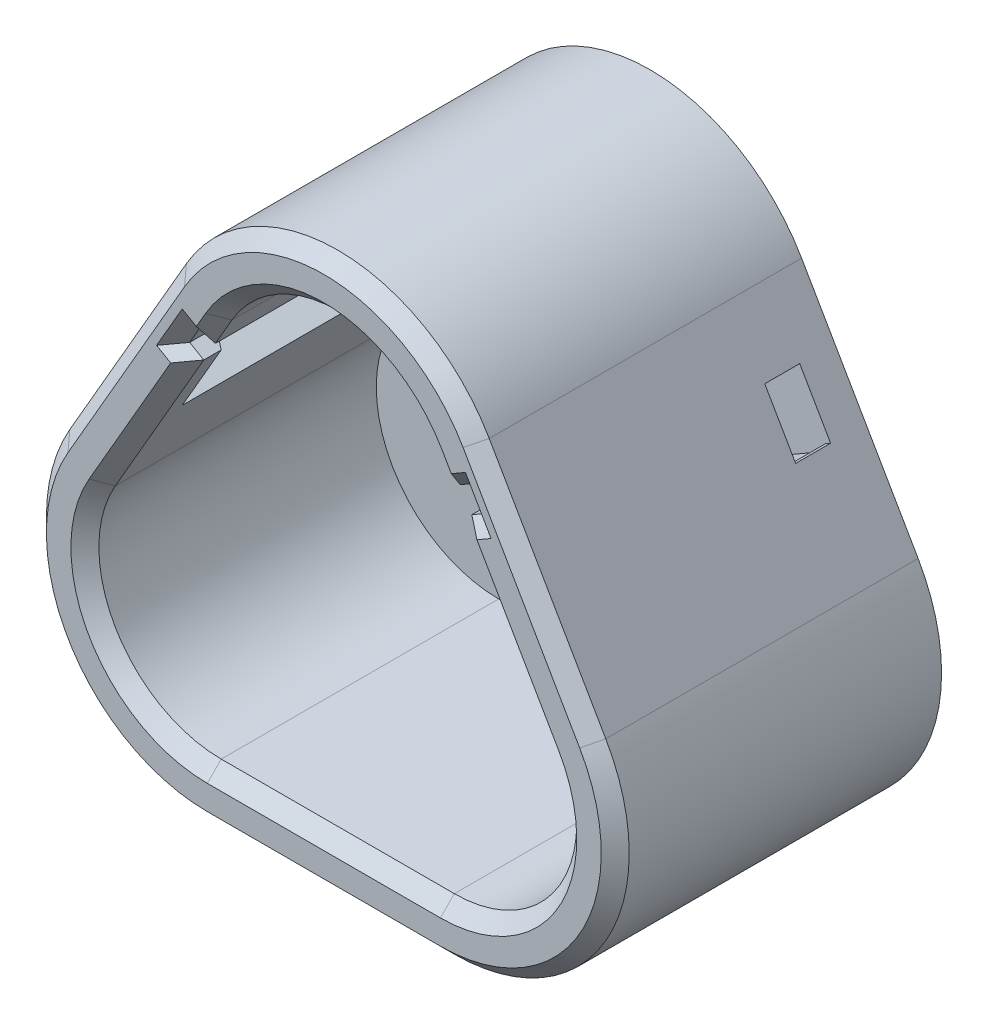
SolidWorks part; units mm, degrees
ref_plane "Plan de face" through (0, 0, 0) normal (0, 0, 1) x (1, 0, 0)
ref_plane "Plan de dessus" through (0, 0, 0) normal (0, 1, 0) x (1, 0, 0)
ref_plane "Plan de droite" through (0, 0, 0) normal (1, 0, 0) x (0, 0, -1)
sketch "Esquisse1" plane through (0, 0, 0) normal (0, 0, 1) x (1, 0, 0)
  line L0 (-18.6603, -0.7735) -> (-8.6603, 16.547)
  line L1 (8.6603, 16.547) -> (18.6603, -0.7735)
  line L2 (-10, -15.7735) -> (10, -15.7735)
  line L3 (0, -15.7735) -> (0, 0) construction
  line L4 (-13.6603, 7.8868) -> (0, 0) construction
  line L5 (13.6603, 7.8868) -> (0, 0) construction
  line L6 (-20, 4.9198) -> (-20, -15.8947) construction
  line L7 (20, 16.147) -> (20, -7.4428) construction
  line L8 (-22.9904, 1.7265) -> (-12.9904, 19.047)
  line L9 (12.9904, 19.047) -> (22.9904, 1.7265)
  line L10 (-10, -20.7735) -> (10, -20.7735)
  arc A0 (-18.6603, -0.7735) -> (-10, -15.7735) centre (-10, -5.7735) ccw
  arc A1 (8.6603, 16.547) -> (-8.6603, 16.547) centre (0, 11.547) ccw
  arc A2 (18.6603, -0.7735) -> (10, -15.7735) centre (10, -5.7735) cw
  arc A3 (12.9904, 19.047) -> (-12.9904, 19.047) centre (0, 11.547) ccw
  arc A4 (22.9904, 1.7265) -> (10, -20.7735) centre (10, -5.7735) cw
  arc A5 (-22.9904, 1.7265) -> (-10, -20.7735) centre (-10, -5.7735) ccw
  point P18 (-20, -5.7735)
  point P19 (0, 21.547)
  point P21 (20, -5.7735)
  dimension "D1" = 10
  dimension "D2" = 40
  dimension "D3" = 5
extrude "Boss.-Extru.1" add sketch "Esquisse1" along normal blind 25
sketch "Esquisse2" plane through (0, 0, 25) normal (0, 0, 1) x (1, 0, 0)
  line L0 (-10.9144, 12.6428) -> (-12.3, 13.4428)
  line L1 (-8.6603, 16.547) -> (-18.6603, -0.7735) construction
  line L2 (-12.3, 13.4428) -> (-11.6, 14.6552)
  line L3 (-11.6, 14.6552) -> (-10.2144, 13.8552)
  line L4 (-10.9144, 12.6428) -> (-10.2144, 13.8552)
  line L5 (10.2144, 13.8552) -> (11.6, 14.6552)
  line L6 (18.6603, -0.7735) -> (8.6603, 16.547) construction
  line L7 (11.6, 14.6552) -> (12.3, 13.4428)
  line L8 (12.3, 13.4428) -> (10.9144, 12.6428)
  line L9 (10.9144, 12.6428) -> (10.2144, 13.8552)
  dimension "D1" = 1.4
  dimension "D2" = 1.6
  dimension "D3" = 24.6
extrude "Enlèv. mat.-Extru.1" cut sketch "Esquisse2" against normal blind 20
sketch "Esquisse3" plane through (0, 0, 25) normal (0, 0, 1) x (1, 0, 0)
  line L0 (-10.0644, 14.115) -> (-11.7098, 15.065)
  line L1 (-8.6603, 16.547) -> (-10.2144, 13.8552) construction
  line L2 (-11.7098, 15.065) -> (-12.7098, 13.333)
  line L3 (-12.7098, 13.333) -> (-11.0644, 12.383)
  line L4 (-10.9144, 12.6428) -> (-18.6603, -0.7735) construction
  line L5 (-11.0644, 12.383) -> (-10.0644, 14.115)
  line L6 (-10.2144, 13.8552) -> (-11.6, 14.6552) construction
  line L7 (-11.6, 14.6552) -> (-12.3, 13.4428) construction
  line L8 (-12.3, 13.4428) -> (-10.9144, 12.6428) construction
  dimension "D1" = 0.3
  dimension "D2" = 0.3
  dimension "D3" = 0.3
extrude "Enlèv. mat.-Extru.2" cut sketch "Esquisse3" against normal through all contours L2 L3 L5 L0
mirror "Symétrie1" about plane through (0, 0, 0) normal (1, 0, 0) of "Enlèv. mat.-Extru.2"
sketch "Esquisse6" plane through (0, 0, 0) normal (0, 0, -1) x (-1, 0, 0)
  line L0 (11.25, 12.0614) -> (15.1471, 14.3114)
  line L1 (11.0644, 12.383) -> (18.6603, -0.7735) construction
  line L2 (15.1471, 14.3114) -> (18.2971, 8.8555)
  line L3 (18.2971, 8.8555) -> (14.4, 6.6055)
  line L4 (14.4, 6.6055) -> (11.25, 12.0614)
  line L5 (-11.25, 12.0614) -> (-15.1471, 14.3114)
  line L6 (-18.6603, -0.7735) -> (-11.0644, 12.383) construction
  line L7 (-15.1471, 14.3114) -> (-18.2971, 8.8555)
  line L8 (-18.2971, 8.8555) -> (-14.4, 6.6055)
  line L9 (-14.4, 6.6055) -> (-11.25, 12.0614)
  point P10 (0, 0)
  point P13 (11.25, 12.0614)
  dimension "D1" = 22.5
  dimension "D2" = 6.3
  dimension "D3" = 4.5
extrude "Enlèv. mat.-Extru.4" cut sketch "Esquisse6" against normal blind 20
sketch "Esquisse5" plane through (0, 0, 25) normal (0, 0, 1) x (1, 0, 0)
  line L1 (-11.0644, 12.383) -> (-18.6603, -0.7735) construction
  line L2 (-10, -15.7735) -> (10, -15.7735) construction
  line L3 (18.6603, -0.7735) -> (11.0644, 12.383) construction
  line L8 (-8.6603, 16.547) -> (-10.0644, 14.115) construction
  line L9 (10.0644, 14.115) -> (8.6603, 16.547) construction
  line L14 (-8.6603, 16.547) -> (-10.0644, 14.115)
  line L15 (10.0644, 14.115) -> (8.6603, 16.547)
  line L19 (18.6603, -0.7735) -> (11.0644, 12.383)
  line L20 (-10, -15.7735) -> (10, -15.7735)
  line L21 (-11.0644, 12.383) -> (-18.6603, -0.7735)
  line L22 (-11.0644, 12.383) -> (-10.0644, 14.115)
  line L23 (11.0644, 12.383) -> (10.0644, 14.115)
  line L24 (-9.0933, 16.797) -> (-10.4974, 14.365)
  line L25 (-11.4974, 12.633) -> (-10.4974, 14.365)
  line L26 (-11.4974, 12.633) -> (-19.0933, -0.5235)
  line L27 (-10, -16.2735) -> (10, -16.2735)
  line L28 (19.0933, -0.5235) -> (11.4974, 12.633)
  line L29 (11.4974, 12.633) -> (10.4974, 14.365)
  line L30 (10.4974, 14.365) -> (9.0933, 16.797)
  arc A0 (-18.6603, -0.7735) -> (-10, -15.7735) centre (-10, -5.7735) ccw construction
  arc A1 (10, -15.7735) -> (18.6603, -0.7735) centre (10, -5.7735) ccw construction
  arc A2 (8.6603, 16.547) -> (-8.6603, 16.547) centre (0, 11.547) ccw construction
  arc A3 (8.6603, 16.547) -> (-8.6603, 16.547) centre (0, 11.547) ccw
  arc A4 (10, -15.7735) -> (18.6603, -0.7735) centre (10, -5.7735) ccw
  arc A5 (-18.6603, -0.7735) -> (-10, -15.7735) centre (-10, -5.7735) ccw
  arc A6 (-19.0933, -0.5235) -> (-10, -16.2735) centre (-10, -5.7735) ccw
  arc A7 (10, -16.2735) -> (19.0933, -0.5235) centre (10, -5.7735) ccw
  arc A8 (9.0933, 16.797) -> (-9.0933, 16.797) centre (0, 11.547) ccw
  dimension "D1" = 0.5
extrude "Enlèv. mat.-Extru.3" cut sketch "Esquisse5" against normal through all
chamfer "Chanfrein1" distance 1.2 angle 45 20 edges at (-11.1036, 14.715, 25) (-12.2098, 14.199, 25) (-12.1036, 12.983, 25) (12.1036, 12.983, 25) (12.2098, 14.199, 25) (11.1036, 14.715, 25) (-17.9904, 10.3868, 25) (0, 26.547, 25) (17.9904, 10.3868, 25) (22.9904, -13.2735, 25) (0, -20.7735, 25) (-22.9904, -13.2735, 25) (0, 22.047, 25) (-9.7953, 15.581, 25) (-15.2953, 6.0547, 25) (-19.0933, -11.0235, 25) (0, -16.2735, 25) (19.0933, -11.0235, 25) (15.2953, 6.0547, 25) (9.7953, 15.581, 25)
sketch "Esquisse4" plane through (0, 0, 0) normal (0, 0, -1) x (-1, 0, 0)
  line L3 (22.9904, 1.7265) -> (12.9904, 19.047)
  line L4 (-12.9904, 19.047) -> (-22.9904, 1.7265)
  line L5 (-10, -20.7735) -> (10, -20.7735)
  line L6 (22.9904, 1.7265) -> (12.9904, 19.047)
  line L7 (-12.9904, 19.047) -> (-22.9904, 1.7265)
  line L8 (-10, -20.7735) -> (10, -20.7735)
  arc A3 (10, -20.7735) -> (22.9904, 1.7265) centre (10, -5.7735) ccw
  arc A4 (12.9904, 19.047) -> (-12.9904, 19.047) centre (0, 11.547) ccw
  arc A5 (-22.9904, 1.7265) -> (-10, -20.7735) centre (-10, -5.7735) ccw
  arc A6 (10, -20.7735) -> (22.9904, 1.7265) centre (10, -5.7735) ccw
  arc A7 (12.9904, 19.047) -> (-12.9904, 19.047) centre (0, 11.547) ccw
  arc A8 (-22.9904, 1.7265) -> (-10, -20.7735) centre (-10, -5.7735) ccw
  dimension "D1" = 0
extrude "Boss.-Extru.2" add sketch "Esquisse4" along normal blind 3
sketch "Esquisse7" plane through (-2.5959, 4.4962, 0) normal (-0.5, 0.866, 0) x (0.866, 0.5, 0)
  line L0 (16.2735, -20) -> (17.6735, -20)
  line L1 (16.2735, -23.8) -> (16.2735, 0) construction
  line L2 (17.6735, -20) -> (17.6735, 0)
  line L3 (17.6735, 0) -> (16.2735, 0)
  line L4 (16.2735, 0) -> (16.2735, -20)
  line L5 (16.2735, -20) -> (20.2735, -20) construction
  line L6 (16.2735, -23.8) -> (17.6735, -23.8) construction
  line L7 (16.2735, 0) -> (20.2735, 0) construction
  point P6 (0, 0)
  point P7 (0, 0)
  point P10 (0, 0)
  point P13 (0, 0)
extrude "Enlèv. mat.-Extru.5" cut sketch "Esquisse7" against normal up to next
mirror "Symétrie2" about plane through (0, 0, 0) normal (1, 0, 0) of "Enlèv. mat.-Extru.5"
chamfer "Chanfrein2" distance 4 angle 30 1 edges at (13.1652, 9.7442, 20) first distance on face at (14.23, 11.5, 20)
sketch "Esquisse8" plane through (17.5574, 10.1368, 0) normal (-0.866, -0.5, 0) x (0, 0, 1)
  line L0 (0, 4.8205) -> (0, -1.4795) construction
  line L1 (3, 4.3205) -> (0, 4.3205)
  line L2 (3, 4.3205) -> (3, -0.9795)
  line L3 (3, -0.9795) -> (0, -0.9795)
  line L4 (0, 4.3205) -> (0, -0.9795)
  line L5 (20, -1.4795) -> (0, -1.4795) construction
  point P4 (0, 0)
  point P5 (0, 0)
  point P6 (0, 0)
  point P9 (0, 1.6705)
  point P10 (2.744, -0.8541)
  dimension "D1" = 0.5
  dimension "D2" = 3
extrude "Enlèv. mat.-Extru.6" cut sketch "Esquisse8" against normal up to next
mirror "Symétrie3" about plane through (0, 0, 0) normal (1, 0, 0) of "Enlèv. mat.-Extru.6"
chamfer "Chanfrein3" distance 4 angle 30 1 edges at (-13.1652, 9.7442, 20) first distance on face at (-14.23, 11.5, 20)
